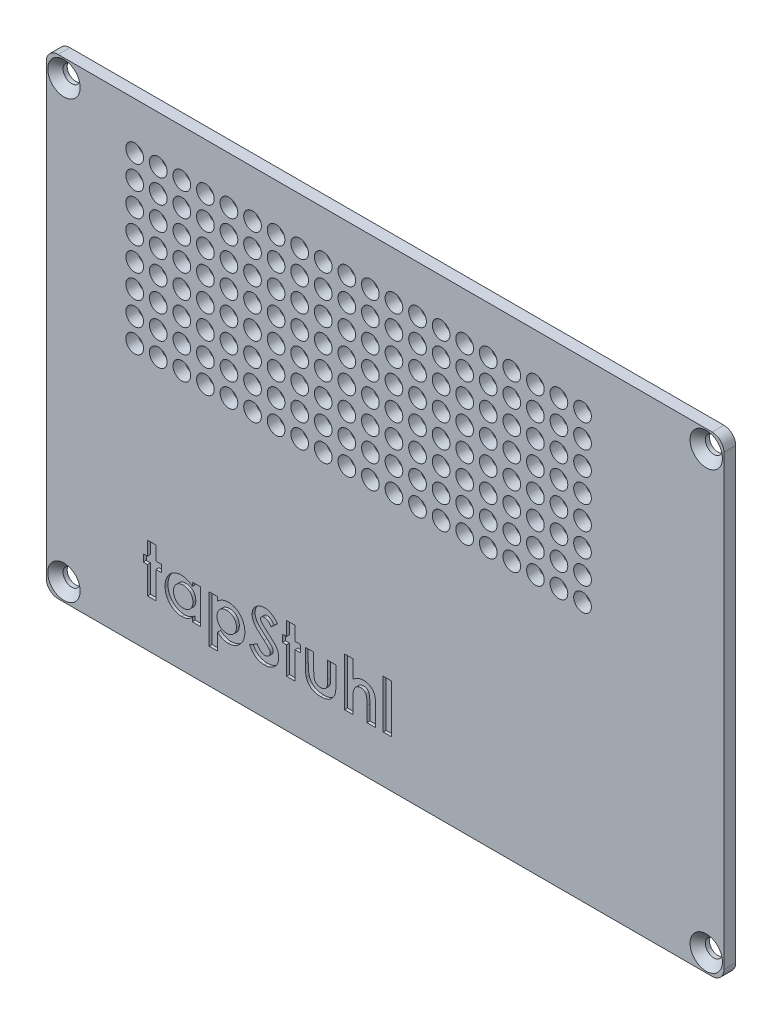
SolidWorks part; units mm, degrees
ref_plane "Ebene vorne" through (0, 0, 0) normal (0, 0, 1) x (1, 0, 0)
ref_plane "Ebene oben" through (0, 0, 0) normal (0, 1, 0) x (1, 0, 0)
ref_plane "Ebene rechts" through (0, 0, 0) normal (1, 0, 0) x (0, 0, -1)
sketch "Sketch1" plane through (0, 0, 0) normal (0, 0, 1) x (1, 0, 0)
  line L4 (113, 80) -> (2, 80)
  line L5 (0, 78) -> (0, 2)
  line L6 (2, 0) -> (113, 0)
  line L7 (115, 2) -> (115, 78)
  line L8 (113, 80) -> (2, 80)
  line L9 (0, 78) -> (0, 2)
  line L10 (2, 0) -> (113, 0)
  line L11 (115, 2) -> (115, 78)
  arc A8 (2, 80) -> (0, 78) centre (2, 78) ccw
  arc A9 (2, 80) -> (0, 78) centre (2, 78) ccw
  arc A10 (0, 2) -> (2, 0) centre (2, 2) ccw
  arc A11 (0, 2) -> (2, 0) centre (2, 2) ccw
  arc A12 (113, 0) -> (115, 2) centre (113, 2) ccw
  arc A13 (113, 0) -> (115, 2) centre (113, 2) ccw
  arc A14 (115, 78) -> (113, 80) centre (113, 78) ccw
  arc A15 (115, 78) -> (113, 80) centre (113, 78) ccw
  dimension "D1" = 0
extrude "Boss-Extrude1" add sketch "Sketch1" along normal blind 2
sketch "Sketch4" plane through (0, 0, 0) normal (0, 0, -1) x (-1, 0, 0)
  line L158 (-112.5, 7.5) -> (-112.5, 72.5) construction
  line L159 (-112.5, 7.5) -> (-107.5, 2.5) construction
  line L160 (-7.5, 2.5) -> (-107.5, 2.5) construction
  line L161 (-7.5, 2.5) -> (-2.5, 7.5) construction
  line L162 (-2.5, 72.5) -> (-2.5, 7.5) construction
  line L163 (-2.5, 72.5) -> (-7.5, 77.5) construction
  line L164 (-107.5, 77.5) -> (-7.5, 77.5) construction
  line L165 (-107.5, 77.5) -> (-112.5, 72.5) construction
  line L166 (-112.5, 7.5) -> (-112.5, 72.5) construction
  line L167 (-112.5, 7.5) -> (-107.5, 2.5) construction
  line L168 (-7.5, 2.5) -> (-107.5, 2.5) construction
  line L169 (-7.5, 2.5) -> (-2.5, 7.5) construction
  line L170 (-2.5, 72.5) -> (-2.5, 7.5) construction
  line L171 (-2.5, 72.5) -> (-7.5, 77.5) construction
  line L172 (-107.5, 77.5) -> (-7.5, 77.5) construction
  line L173 (-107.5, 77.5) -> (-112.5, 72.5) construction
  line L174 (-112.3, 7.5828) -> (-112.3, 72.4172)
  line L175 (-107.4172, 77.3) -> (-112.3, 72.4172)
  line L176 (-107.4172, 77.3) -> (-7.5828, 77.3)
  line L177 (-2.7, 72.4172) -> (-7.5828, 77.3)
  line L178 (-2.7, 72.4172) -> (-2.7, 7.5828)
  line L179 (-7.5828, 2.7) -> (-2.7, 7.5828)
  line L180 (-7.5828, 2.7) -> (-107.4172, 2.7)
  line L181 (-112.3, 7.5828) -> (-107.4172, 2.7)
  line L182 (-110.3, 8.4113) -> (-110.3, 71.5887)
  line L183 (-106.5887, 75.3) -> (-110.3, 71.5887)
  line L184 (-106.5887, 75.3) -> (-8.4113, 75.3)
  line L185 (-4.7, 71.5887) -> (-8.4113, 75.3)
  line L186 (-4.7, 71.5887) -> (-4.7, 8.4113)
  line L187 (-8.4113, 4.7) -> (-4.7, 8.4113)
  line L188 (-8.4113, 4.7) -> (-106.5887, 4.7)
  line L189 (-110.3, 8.4113) -> (-106.5887, 4.7)
  dimension "D1" = 0.2
  dimension "D2" = 2
extrude "Boss-Extrude2" add sketch "Sketch4" along normal blind 1
sketch "Sketch5" plane through (0, 0, 2) normal (0, 0, 1) x (1, 0, 0)
  line L0 (0, 78) -> (0, 2) construction
  line L1 (113, 80) -> (2, 80) construction
  line L2 (15, 72) -> (19, 72) construction
  line L3 (15, 72) -> (15, 68) construction
  circle A0 centre (15, 72) radius 1.5
  circle A1 centre (19, 72) radius 1.5
  circle A2 centre (23, 72) radius 1.5
  circle A3 centre (27, 72) radius 1.5
  circle A4 centre (31, 72) radius 1.5
  circle A5 centre (35, 72) radius 1.5
  circle A6 centre (39, 72) radius 1.5
  circle A7 centre (43, 72) radius 1.5
  circle A8 centre (19, 68) radius 1.5
  circle A9 centre (23, 68) radius 1.5
  circle A10 centre (27, 68) radius 1.5
  circle A11 centre (31, 68) radius 1.5
  circle A12 centre (35, 68) radius 1.5
  circle A13 centre (39, 68) radius 1.5
  circle A14 centre (43, 68) radius 1.5
  circle A15 centre (19, 64) radius 1.5
  circle A16 centre (23, 64) radius 1.5
  circle A17 centre (27, 64) radius 1.5
  circle A18 centre (31, 64) radius 1.5
  circle A19 centre (35, 64) radius 1.5
  circle A20 centre (39, 64) radius 1.5
  circle A21 centre (43, 64) radius 1.5
  circle A22 centre (19, 60) radius 1.5
  circle A23 centre (23, 60) radius 1.5
  circle A24 centre (27, 60) radius 1.5
  circle A25 centre (31, 60) radius 1.5
  circle A26 centre (35, 60) radius 1.5
  circle A27 centre (39, 60) radius 1.5
  circle A28 centre (43, 60) radius 1.5
  circle A29 centre (15, 68) radius 1.5
  circle A30 centre (15, 64) radius 1.5
  circle A31 centre (15, 60) radius 1.5
  circle A40 centre (15, 56) radius 1.5
  circle A41 centre (19, 56) radius 1.5
  circle A42 centre (23, 56) radius 1.5
  circle A43 centre (27, 56) radius 1.5
  circle A44 centre (31, 56) radius 1.5
  circle A45 centre (35, 56) radius 1.5
  circle A46 centre (39, 56) radius 1.5
  circle A47 centre (43, 56) radius 1.5
  circle A50 centre (15, 52) radius 1.5
  circle A51 centre (19, 52) radius 1.5
  circle A52 centre (23, 52) radius 1.5
  circle A53 centre (27, 52) radius 1.5
  circle A54 centre (31, 52) radius 1.5
  circle A55 centre (35, 52) radius 1.5
  circle A56 centre (39, 52) radius 1.5
  circle A57 centre (43, 52) radius 1.5
  circle A60 centre (15, 48) radius 1.5
  circle A61 centre (19, 48) radius 1.5
  circle A62 centre (23, 48) radius 1.5
  circle A63 centre (27, 48) radius 1.5
  circle A64 centre (31, 48) radius 1.5
  circle A65 centre (35, 48) radius 1.5
  circle A66 centre (39, 48) radius 1.5
  circle A67 centre (43, 48) radius 1.5
  circle A68 centre (47, 72) radius 1.5
  circle A69 centre (51, 72) radius 1.5
  circle A70 centre (47, 68) radius 1.5
  circle A71 centre (51, 68) radius 1.5
  circle A72 centre (47, 64) radius 1.5
  circle A73 centre (51, 64) radius 1.5
  circle A74 centre (47, 60) radius 1.5
  circle A75 centre (51, 60) radius 1.5
  circle A76 centre (47, 56) radius 1.5
  circle A77 centre (51, 56) radius 1.5
  circle A78 centre (47, 52) radius 1.5
  circle A79 centre (51, 52) radius 1.5
  circle A80 centre (47, 48) radius 1.5
  circle A81 centre (51, 48) radius 1.5
  circle A82 centre (55, 72) radius 1.5
  circle A83 centre (59, 72) radius 1.5
  circle A84 centre (63, 72) radius 1.5
  circle A85 centre (67, 72) radius 1.5
  circle A86 centre (71, 72) radius 1.5
  circle A87 centre (75, 72) radius 1.5
  circle A88 centre (79, 72) radius 1.5
  circle A89 centre (83, 72) radius 1.5
  circle A90 centre (87, 72) radius 1.5
  circle A91 centre (91, 72) radius 1.5
  circle A92 centre (55, 68) radius 1.5
  circle A93 centre (59, 68) radius 1.5
  circle A94 centre (63, 68) radius 1.5
  circle A95 centre (67, 68) radius 1.5
  circle A96 centre (71, 68) radius 1.5
  circle A97 centre (75, 68) radius 1.5
  circle A98 centre (79, 68) radius 1.5
  circle A99 centre (83, 68) radius 1.5
  circle A100 centre (87, 68) radius 1.5
  circle A101 centre (91, 68) radius 1.5
  circle A102 centre (55, 64) radius 1.5
  circle A103 centre (59, 64) radius 1.5
  circle A104 centre (63, 64) radius 1.5
  circle A105 centre (67, 64) radius 1.5
  circle A106 centre (71, 64) radius 1.5
  circle A107 centre (75, 64) radius 1.5
  circle A108 centre (79, 64) radius 1.5
  circle A109 centre (83, 64) radius 1.5
  circle A110 centre (87, 64) radius 1.5
  circle A111 centre (91, 64) radius 1.5
  circle A112 centre (55, 60) radius 1.5
  circle A113 centre (59, 60) radius 1.5
  circle A114 centre (63, 60) radius 1.5
  circle A115 centre (67, 60) radius 1.5
  circle A116 centre (71, 60) radius 1.5
  circle A117 centre (75, 60) radius 1.5
  circle A118 centre (79, 60) radius 1.5
  circle A119 centre (83, 60) radius 1.5
  circle A120 centre (87, 60) radius 1.5
  circle A121 centre (91, 60) radius 1.5
  circle A122 centre (55, 56) radius 1.5
  circle A123 centre (59, 56) radius 1.5
  circle A124 centre (63, 56) radius 1.5
  circle A125 centre (67, 56) radius 1.5
  circle A126 centre (71, 56) radius 1.5
  circle A127 centre (75, 56) radius 1.5
  circle A128 centre (79, 56) radius 1.5
  circle A129 centre (83, 56) radius 1.5
  circle A130 centre (87, 56) radius 1.5
  circle A131 centre (91, 56) radius 1.5
  circle A132 centre (55, 52) radius 1.5
  circle A133 centre (59, 52) radius 1.5
  circle A134 centre (63, 52) radius 1.5
  circle A135 centre (67, 52) radius 1.5
  circle A136 centre (71, 52) radius 1.5
  circle A137 centre (75, 52) radius 1.5
  circle A138 centre (79, 52) radius 1.5
  circle A139 centre (83, 52) radius 1.5
  circle A140 centre (87, 52) radius 1.5
  circle A141 centre (91, 52) radius 1.5
  circle A142 centre (55, 48) radius 1.5
  circle A143 centre (59, 48) radius 1.5
  circle A144 centre (63, 48) radius 1.5
  circle A145 centre (67, 48) radius 1.5
  circle A146 centre (71, 48) radius 1.5
  circle A147 centre (75, 48) radius 1.5
  circle A148 centre (79, 48) radius 1.5
  circle A149 centre (83, 48) radius 1.5
  circle A150 centre (87, 48) radius 1.5
  circle A151 centre (91, 48) radius 1.5
  circle A152 centre (15, 44) radius 1.5
  circle A153 centre (19, 44) radius 1.5
  circle A154 centre (23, 44) radius 1.5
  circle A155 centre (27, 44) radius 1.5
  circle A156 centre (31, 44) radius 1.5
  circle A157 centre (35, 44) radius 1.5
  circle A158 centre (39, 44) radius 1.5
  circle A159 centre (43, 44) radius 1.5
  circle A160 centre (47, 44) radius 1.5
  circle A161 centre (51, 44) radius 1.5
  circle A162 centre (55, 44) radius 1.5
  circle A163 centre (59, 44) radius 1.5
  circle A164 centre (63, 44) radius 1.5
  circle A165 centre (67, 44) radius 1.5
  circle A166 centre (71, 44) radius 1.5
  circle A167 centre (75, 44) radius 1.5
  circle A168 centre (79, 44) radius 1.5
  circle A169 centre (83, 44) radius 1.5
  circle A170 centre (87, 44) radius 1.5
  circle A171 centre (91, 44) radius 1.5
  dimension "D1" = 3
  dimension "D2" = 15
  dimension "D3" = 8
  dimension "D6" = 4
  dimension "D7" = 4
  dimension "D4" = 20
  dimension "D5" = 8
extrude "Cut-Extrude1" cut sketch "Sketch5" against normal through all
sketch "Sketch7" plane through (0, 0, 2) normal (0, 0, 1) x (1, 0, 0)
  circle A0 centre (3, 77) radius 1.15 construction
  circle A1 centre (3, 3) radius 1.15 construction
  circle A2 centre (112, 77) radius 1.15 construction
  circle A3 centre (112, 3) radius 1.15 construction
  point P0 (112, 77)
  point P1 (3, 77)
  point P3 (3, 3)
  point P4 (112, 3)
hole_wizard "CSK for M2.5 Countersunk Flat Head Screw1" positions "Sketch10" profile "Sketch11" countersink size "M2.5" standard "DIN" end condition up to next
sketch "Sketch10" plane through (0, 0, 2) normal (0, 0, 1) x (1, 0, 0)
  point P0 (3, 77)
  point P3 (3, 3)
  point P6 (112, 3)
  point P9 (112, 77)
sketch "Sketch11" plane through (3, 77, 2) normal (1, 0, 0) x (0, -1, 0)
  line L0 (0, 0) -> (0, 2)
  line L1 (0, 2) -> (1.45, 2)
  line L2 (1.45, 2) -> (1.45, 1.3)
  line L3 (1.45, 1.3) -> (2.75, 0)
  line L5 (2.75, 0) -> (0, 0)
  line L6 (-1.45, 1.3) -> (-2.75, 0) construction
  line L11 (0, -6.35) -> (0, 107.95) construction
  dimension "Thru Hole Dia." = 2.9
  dimension "Thru Hole Depth" = 2
  dimension "Near C'Sink Dia." = 5.5
  dimension "Near C'Sink Angle" = 90
sketch "Sketch12" plane through (0, 0, 2) normal (0, 0, 1) x (1, 0, 0)
  line L0 (16.3642, 8) -> (115, 8) construction
  line L2 (115, 2) -> (115, 78) construction
  line L3 (2, 0) -> (113, 0) construction
  line L4 (16.3642, 48.6237) -> (16.3642, 8) construction
  circle A0 centre (15, 48) radius 1.5 construction
  text T0 "tapStuhl" font "Century Gothic" height 8
  dimension "D1" = 8
extrude "Cut-Extrude2" cut sketch "Sketch12" against normal blind 0.5
